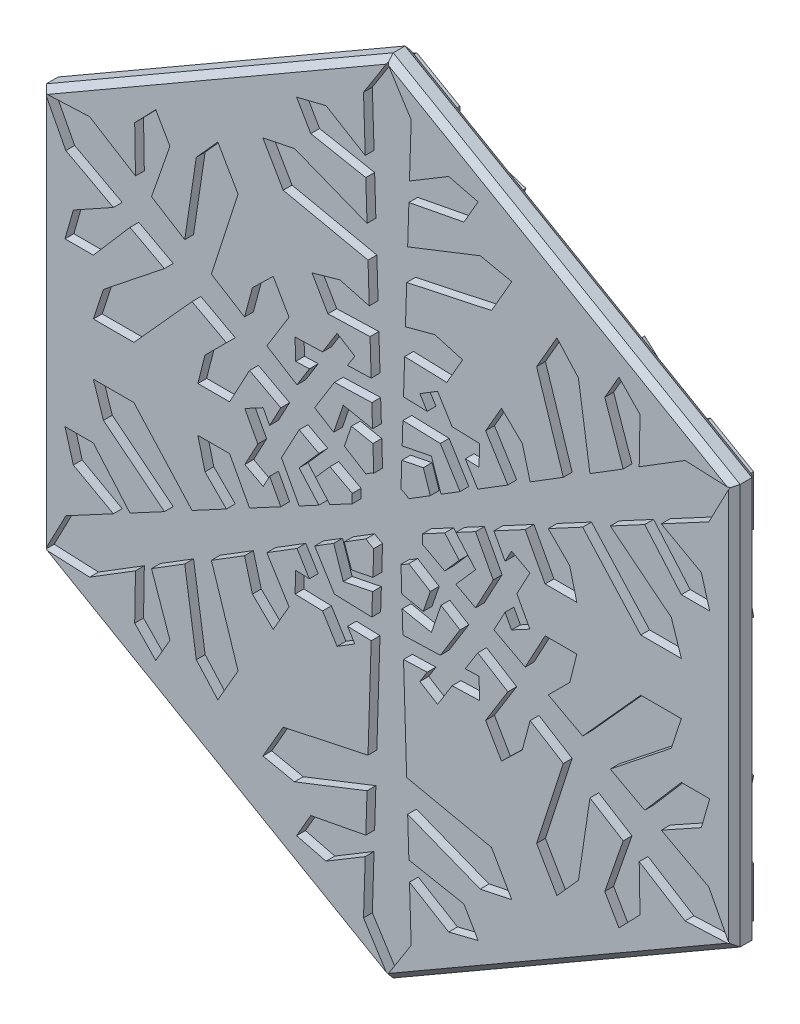
SolidWorks part; units mm, degrees
ref_plane "정면" through (0, 0, 0) normal (0, 0, 1) x (1, 0, 0)
ref_plane "윗면" through (0, 0, 0) normal (0, 1, 0) x (1, 0, 0)
ref_plane "우측면" through (0, 0, 0) normal (1, 0, 0) x (0, 0, -1)
sketch "스케치1" plane through (0, 0, 0) normal (0, 0, 1) x (1, 0, 0)
  line L0 (0, 0) -> (-56.2917, 32.5)
  line L1 (58.8897, -34) -> (58.8897, 34)
  line L2 (58.8897, 34) -> (0, 68)
  line L3 (0, 68) -> (-58.8897, 34)
  line L4 (-58.8897, 34) -> (-58.8897, -34)
  line L5 (-58.8897, -34) -> (0, -68)
  line L6 (0, -68) -> (58.8897, -34)
  line L7 (56.2917, 32.5) -> (0, 0)
  line L8 (0, -65) -> (0, 0)
  line L9 (-56.2917, 32.5) -> (-56.2917, -32.5)
  line L10 (-56.2917, -32.5) -> (0, -65)
  line L11 (0, -65) -> (56.2917, -32.5)
  line L12 (56.2917, -32.5) -> (56.2917, 32.5)
  line L13 (56.2917, 32.5) -> (0, 65)
  line L14 (0, 65) -> (-56.2917, 32.5)
  circle A1 centre (0, 0) radius 58.8897 construction
  point P1 (-58, 34.641)
  point P11 (0, -5)
  point P15 (0, -10)
  point P17 (-59, 32.909)
  point P20 (0, -15)
  point P21 (0, -20)
  point P22 (0, -25)
  point P23 (0, -30)
  point P24 (0, -35)
  point P25 (0, -40)
  point P26 (0, -45)
  point P27 (0, -50)
  point P28 (0, -55)
  point P29 (0, -60)
  point P32 (-4.3301, 2.3594)
  point P33 (-8.6603, 4.8594)
  point P34 (-12.9904, 7.3594)
  point P35 (-17.3205, 9.8594)
  point P36 (-21.6506, 12.3594)
  point P37 (-25.9808, 14.8594)
  point P38 (-30.3109, 17.3594)
  point P39 (-34.641, 19.8594)
  point P40 (-38.9711, 22.3594)
  point P41 (-43.3013, 24.8594)
  point P42 (-47.6314, 27.3594)
  point P43 (-51.9615, 29.8594)
  point P44 (4.2083, 2.4297)
  point P45 (8.5385, 4.9297)
  point P46 (12.8686, 7.4297)
  point P47 (17.1987, 9.9297)
  point P48 (21.5289, 12.4297)
  point P49 (25.859, 14.9297)
  point P50 (30.1891, 17.4297)
  point P51 (34.5192, 19.9297)
  point P52 (38.8494, 22.4297)
  point P53 (43.1795, 24.9297)
  point P54 (47.5096, 27.4297)
  point P55 (51.8397, 29.9297)
  point P56 (-0.0406, -0.0703)
  dimension "D1" = 65
  dimension "D2" = 5
  dimension "D3" = 12
  dimension "D4" = 3
  dimension "D5" = 65
  dimension "D6" = 65
  dimension "D7" = 65
  dimension "D8" = 68
extrude "보스-돌출1" add sketch "스케치1" along normal blind 5 contours L4 L5 L6 L1 L2 L3
sketch "스케치6" plane through (0, 0, 5) normal (0, 0, 1) x (1, 0, 0)
  line L1 (-58.8897, 34) -> (-58.0516, 33.5161)
  line L2 (-58.8897, 34) -> (-58.8897, -34)
  line L3 (0, 0) -> (-58.8897, 0) construction
  line L4 (-58.8897, -34) -> (0, -68)
  line L5 (0, -68) -> (0, 0)
  line L6 (0, 0) -> (-29.4449, -51) construction
  line L7 (-33.1527, -15.3513) -> (-27.313, -12.2197)
  line L8 (-54.5739, -26.8389) -> (-46.5066, -22.5127)
  line L9 (-46.5066, -22.5127) -> (-53.2967, -18.748)
  line L10 (-53.2967, -18.748) -> (-54.7146, -13.8014)
  line L11 (-54.7146, -13.8014) -> (-49.9016, -13.8014)
  line L12 (-49.9016, -13.8014) -> (-43.6834, -20.9987)
  line L13 (-37.8382, -17.864) -> (-48.1939, -9.622)
  line L14 (-48.1939, -9.622) -> (-49.9016, -4.4211)
  line L15 (-49.9016, -4.4211) -> (-43.0161, -4.4211)
  line L16 (-43.0161, -4.4211) -> (-33.1527, -15.3513)
  line L17 (-27.313, -12.2197) -> (-30.9566, -8.576)
  line L18 (-30.9566, -8.576) -> (-32.1611, -3.8066)
  line L19 (-32.1611, -3.8066) -> (-26.7746, -3.8066)
  line L20 (-26.7746, -3.8066) -> (-23.3909, -10.1164)
  line L21 (-18.0861, -7.2716) -> (-19.9799, -3.7402)
  line L22 (-24.196, 4.1218) -> (-21.0805, 5.7925)
  line L23 (-21.0805, 5.7925) -> (-19.9799, 3.7402)
  line L24 (-11.6248, -3.8066) -> (-14.9706, 0)
  line L25 (8.9871, -15.5661) -> (12.3358, -10.1645)
  line L26 (-12.1952, 0) -> (-9.7385, -2.795)
  line L27 (-50.5302, -33.8429) -> (-42.7498, -29.0196)
  line L28 (-6.0976, -10.5614) -> (-7.2898, -7.0363)
  line L29 (-43.6834, 20.9987) -> (-37.8382, 17.864)
  line L30 (-9.109, -8.1641) -> (-7.4853, -12.9649)
  line L31 (-5.5238, -21.1525) -> (-6.7509, -19.1732)
  line L32 (-8.5285, -23.0152) -> (-5.5238, -21.1525)
  line L33 (-15.3404, -12.0272) -> (-13.229, -15.433)
  line L34 (-16.6839, -21.2842) -> (-20.4564, -15.1989)
  line L35 (-19.3771, -25.9491) -> (-16.6839, -21.2842)
  line L36 (-22.9054, -22.5212) -> (-19.3771, -25.9491)
  line L37 (-24.239, -17.5439) -> (-22.9054, -22.5212)
  line L38 (-25.3368, -35.0424) -> (-29.871, -21.0354)
  line L39 (-28.7796, -41.0055) -> (-25.3368, -35.0424)
  line L40 (-32.4298, -36.9262) -> (-28.7796, -41.0055)
  line L41 (-34.3898, -23.8368) -> (-32.4298, -36.9262)
  line L42 (-36.9032, -36.3154) -> (-40.0271, -27.3316)
  line L43 (-39.3097, -40.4835) -> (-36.9032, -36.3154)
  line L44 (-42.8846, -36.7823) -> (-39.3097, -40.4835)
  line L45 (-42.7498, -29.0196) -> (-42.8846, -36.7823)
  line L48 (-50.5302, 33.8429) -> (-42.7498, 29.0196)
  line L49 (-42.7498, 29.0196) -> (-42.8846, 36.7823)
  line L50 (-42.8846, 36.7823) -> (-39.3097, 40.4835)
  line L51 (-39.3097, 40.4835) -> (-36.9032, 36.3154)
  line L52 (-36.9032, 36.3154) -> (-40.0271, 27.3316)
  line L53 (-34.3898, 23.8368) -> (-32.4298, 36.9262)
  line L54 (-32.4298, 36.9262) -> (-28.7796, 41.0055)
  line L55 (-28.7796, 41.0055) -> (-25.3368, 35.0424)
  line L56 (-25.3368, 35.0424) -> (-29.871, 21.0354)
  line L57 (-24.239, 17.5439) -> (-22.9054, 22.5212)
  line L58 (-22.9054, 22.5212) -> (-19.3771, 25.9491)
  line L59 (-19.3771, 25.9491) -> (-16.6839, 21.2842)
  line L60 (-16.6839, 21.2842) -> (-20.4564, 15.1989)
  line L61 (-15.3404, 12.0272) -> (-13.229, 15.433)
  line L62 (-9.109, 8.1641) -> (-7.4853, 12.9649)
  line L63 (-40.0271, 27.3316) -> (-34.3898, 23.8368)
  line L64 (-6.0976, 10.5614) -> (-7.2898, 7.0363)
  line L65 (-54.5739, 26.8389) -> (-46.5066, 22.5127)
  line L66 (-12.1952, 0) -> (-9.7385, 2.795)
  line L67 (-14.9706, 0) -> (-12.1952, 0)
  line L68 (-11.6248, 3.8066) -> (-14.9706, 0)
  line L69 (-21.0805, -5.7925) -> (-19.9799, -3.7402)
  line L70 (-24.196, -4.1218) -> (-21.0805, -5.7925)
  line L71 (-18.0861, 7.2716) -> (-19.9799, 3.7402)
  line L72 (-26.7746, 3.8066) -> (-23.3909, 10.1164)
  line L73 (-32.1611, 3.8066) -> (-26.7746, 3.8066)
  line L74 (-30.9566, 8.576) -> (-32.1611, 3.8066)
  line L75 (-27.313, 12.2197) -> (-30.9566, 8.576)
  line L76 (-43.0161, 4.4211) -> (-33.1527, 15.3513)
  line L77 (-49.9016, 4.4211) -> (-43.0161, 4.4211)
  line L78 (-48.1939, 9.622) -> (-49.9016, 4.4211)
  line L79 (-37.8382, 17.864) -> (-48.1939, 9.622)
  line L80 (-49.9016, 13.8014) -> (-43.6834, 20.9987)
  line L81 (-54.7146, 13.8014) -> (-49.9016, 13.8014)
  line L82 (-53.2967, 18.748) -> (-54.7146, 13.8014)
  line L83 (-46.5066, 22.5127) -> (-53.2967, 18.748)
  line L85 (-5.5238, 21.1525) -> (-6.7509, 19.1732)
  line L86 (-8.5285, 23.0152) -> (-5.5238, 21.1525)
  line L88 (4.0438, 60.6819) -> (3.7568, 51.5322)
  line L89 (3.7568, 51.5322) -> (10.4121, 55.5303)
  line L90 (10.4121, 55.5303) -> (15.4049, 54.285)
  line L91 (15.4049, 54.285) -> (12.9984, 50.1168)
  line L92 (12.9984, 50.1168) -> (3.6563, 48.3303)
  line L93 (3.4484, 41.7008) -> (15.7641, 46.5482)
  line L94 (15.7641, 46.5482) -> (21.122, 45.4266)
  line L95 (21.122, 45.4266) -> (17.6792, 39.4635)
  line L96 (17.6792, 39.4635) -> (3.2817, 36.3867)
  line L97 (3.0739, 29.7636) -> (8.0512, 31.0972)
  line L98 (8.0512, 31.0972) -> (12.784, 29.7556)
  line L99 (12.784, 29.7556) -> (10.0907, 25.0908)
  line L100 (10.0907, 25.0908) -> (2.9344, 25.3153)
  line L101 (2.7457, 19.2988) -> (6.7509, 19.1732)
  line L102 (2.5158, 11.9706) -> (7.4853, 12.9649)
  line L103 (-29.871, 21.0354) -> (-24.239, 17.5439)
  line L104 (6.0976, 10.5614) -> (2.4487, 9.8313)
  line L105 (-4.0438, 60.6819) -> (-3.7568, 51.5322)
  line L106 (-6.0976, 10.5614) -> (-2.4487, 9.8313)
  line L107 (-33.1527, 15.3513) -> (-27.313, 12.2197)
  line L108 (-2.5158, 11.9706) -> (-7.4853, 12.9649)
  line L109 (-15.5567, 15.36) -> (-13.229, 15.433)
  line L110 (-15.6676, 18.8935) -> (-15.5567, 15.36)
  line L111 (-2.7457, 19.2988) -> (-6.7509, 19.1732)
  line L112 (-10.0907, 25.0908) -> (-2.9344, 25.3153)
  line L113 (-12.784, 29.7556) -> (-10.0907, 25.0908)
  line L114 (-8.0512, 31.0972) -> (-12.784, 29.7556)
  line L115 (-3.0739, 29.7636) -> (-8.0512, 31.0972)
  line L116 (-17.6792, 39.4635) -> (-3.2817, 36.3867)
  line L117 (-21.122, 45.4266) -> (-17.6792, 39.4635)
  line L118 (-15.7641, 46.5482) -> (-21.122, 45.4266)
  line L119 (-3.4484, 41.7008) -> (-15.7641, 46.5482)
  line L120 (-12.9984, 50.1168) -> (-3.6563, 48.3303)
  line L121 (-15.4049, 54.285) -> (-12.9984, 50.1168)
  line L122 (-10.4121, 55.5303) -> (-15.4049, 54.285)
  line L123 (-3.7568, 51.5322) -> (-10.4121, 55.5303)
  line L125 (15.5567, 15.36) -> (13.229, 15.433)
  line L126 (15.6676, 18.8935) -> (15.5567, 15.36)
  line L128 (54.5739, 26.8389) -> (46.5066, 22.5127)
  line L129 (46.5066, 22.5127) -> (53.2967, 18.748)
  line L130 (53.2967, 18.748) -> (54.7146, 13.8014)
  line L131 (54.7146, 13.8014) -> (49.9016, 13.8014)
  line L132 (49.9016, 13.8014) -> (43.6834, 20.9987)
  line L133 (37.8382, 17.864) -> (48.1939, 9.622)
  line L134 (48.1939, 9.622) -> (49.9016, 4.4211)
  line L135 (49.9016, 4.4211) -> (43.0161, 4.4211)
  line L136 (43.0161, 4.4211) -> (33.1527, 15.3513)
  line L137 (27.313, 12.2197) -> (30.9566, 8.576)
  line L138 (30.9566, 8.576) -> (32.1611, 3.8066)
  line L139 (32.1611, 3.8066) -> (26.7746, 3.8066)
  line L140 (26.7746, 3.8066) -> (23.3909, 10.1164)
  line L141 (18.0861, 7.2716) -> (19.9799, 3.7402)
  line L142 (11.6248, 3.8066) -> (14.9706, 0)
  line L143 (-20.4564, 15.1989) -> (-15.3404, 12.0272)
  line L144 (12.1952, 0) -> (9.7385, 2.795)
  line L145 (50.5302, 33.8429) -> (42.7498, 29.0196)
  line L146 (6.0976, 10.5614) -> (7.2898, 7.0363)
  line L147 (7.2898, 7.0363) -> (3.6372, 4.7719)
  line L148 (9.109, 8.1641) -> (7.4853, 12.9649)
  line L149 (5.5238, 21.1525) -> (6.7509, 19.1732)
  line L150 (8.5285, 23.0152) -> (5.5238, 21.1525)
  line L151 (15.3404, 12.0272) -> (13.229, 15.433)
  line L152 (16.6839, 21.2842) -> (20.4564, 15.1989)
  line L153 (19.3771, 25.9491) -> (16.6839, 21.2842)
  line L154 (22.9054, 22.5212) -> (19.3771, 25.9491)
  line L155 (24.239, 17.5439) -> (22.9054, 22.5212)
  line L156 (25.3368, 35.0424) -> (29.871, 21.0354)
  line L157 (28.7796, 41.0055) -> (25.3368, 35.0424)
  line L158 (32.4298, 36.9262) -> (28.7796, 41.0055)
  line L159 (34.3898, 23.8368) -> (32.4298, 36.9262)
  line L160 (36.9032, 36.3154) -> (40.0271, 27.3316)
  line L161 (39.3097, 40.4835) -> (36.9032, 36.3154)
  line L162 (42.8846, 36.7823) -> (39.3097, 40.4835)
  line L163 (42.7498, 29.0196) -> (42.8846, 36.7823)
  line L165 (21.0805, -5.7925) -> (19.9799, -3.7402)
  line L166 (24.196, -4.1218) -> (21.0805, -5.7925)
  line L168 (50.5302, -33.8429) -> (42.7498, -29.0196)
  line L169 (42.7498, -29.0196) -> (42.8846, -36.7823)
  line L170 (42.8846, -36.7823) -> (39.3097, -40.4835)
  line L171 (39.3097, -40.4835) -> (36.9032, -36.3154)
  line L172 (36.9032, -36.3154) -> (40.0271, -27.3316)
  line L173 (34.3898, -23.8368) -> (32.4298, -36.9262)
  line L174 (32.4298, -36.9262) -> (28.7796, -41.0055)
  line L175 (28.7796, -41.0055) -> (25.3368, -35.0424)
  line L176 (25.3368, -35.0424) -> (29.871, -21.0354)
  line L177 (24.239, -17.5439) -> (22.9054, -22.5212)
  line L178 (22.9054, -22.5212) -> (19.3771, -25.9491)
  line L179 (19.3771, -25.9491) -> (16.6839, -21.2842)
  line L180 (16.6839, -21.2842) -> (20.4564, -15.1989)
  line L181 (15.3404, -12.0272) -> (13.229, -15.433)
  line L182 (9.109, -8.1641) -> (7.4853, -12.9649)
  line L183 (-23.3909, 10.1164) -> (-18.0861, 7.2716)
  line L184 (6.0976, -10.5614) -> (7.2898, -7.0363)
  line L185 (54.5739, -26.8389) -> (46.5066, -22.5127)
  line L186 (12.1952, 0) -> (9.7385, -2.795)
  line L187 (-3.6563, 48.3303) -> (-3.4484, 41.7008)
  line L188 (11.6248, -3.8066) -> (14.9706, 0)
  line L189 (21.0805, 5.7925) -> (19.9799, 3.7402)
  line L190 (24.196, 4.1218) -> (21.0805, 5.7925)
  line L191 (18.0861, -7.2716) -> (19.9799, -3.7402)
  line L192 (26.7746, -3.8066) -> (23.3909, -10.1164)
  line L193 (32.1611, -3.8066) -> (26.7746, -3.8066)
  line L194 (30.9566, -8.576) -> (32.1611, -3.8066)
  line L195 (27.313, -12.2197) -> (30.9566, -8.576)
  line L196 (43.0161, -4.4211) -> (33.1527, -15.3513)
  line L197 (49.9016, -4.4211) -> (43.0161, -4.4211)
  line L198 (48.1939, -9.622) -> (49.9016, -4.4211)
  line L199 (37.8382, -17.864) -> (48.1939, -9.622)
  line L200 (49.9016, -13.8014) -> (43.6834, -20.9987)
  line L201 (54.7146, -13.8014) -> (49.9016, -13.8014)
  line L202 (53.2967, -18.748) -> (54.7146, -13.8014)
  line L203 (46.5066, -22.5127) -> (53.2967, -18.748)
  line L205 (5.5238, -21.1525) -> (6.7509, -19.1732)
  line L206 (8.5285, -23.0152) -> (5.5238, -21.1525)
  line L208 (-4.0438, -60.6819) -> (-3.7568, -51.5322)
  line L209 (-3.7568, -51.5322) -> (-10.4121, -55.5303)
  line L210 (-10.4121, -55.5303) -> (-15.4049, -54.285)
  line L211 (-15.4049, -54.285) -> (-12.9984, -50.1168)
  line L212 (-12.9984, -50.1168) -> (-3.6563, -48.3303)
  line L213 (-3.4484, -41.7008) -> (-15.7641, -46.5482)
  line L214 (-15.7641, -46.5482) -> (-21.122, -45.4266)
  line L215 (-21.122, -45.4266) -> (-17.6792, -39.4635)
  line L216 (-17.6792, -39.4635) -> (-3.2817, -36.3867)
  line L217 (-3.0739, -29.7636) -> (-8.0512, -31.0972)
  line L218 (-8.0512, -31.0972) -> (-12.784, -29.7556)
  line L219 (-12.784, -29.7556) -> (-10.0907, -25.0908)
  line L220 (-10.0907, -25.0908) -> (-2.9344, -25.3153)
  line L221 (-2.7457, -19.2988) -> (-6.7509, -19.1732)
  line L222 (-2.5158, -11.9706) -> (-7.4853, -12.9649)
  line L223 (-7.4853, -12.9649) -> (-6.0976, -10.5614)
  line L224 (-6.0976, -10.5614) -> (-2.4487, -9.8313)
  line L225 (4.0438, -60.6819) -> (3.7568, -51.5322)
  line L226 (6.0976, -10.5614) -> (2.4487, -9.8313)
  line L227 (3.6563, 48.3303) -> (3.4484, 41.7008)
  line L228 (2.5158, -11.9706) -> (7.4853, -12.9649)
  line L229 (15.5567, -15.36) -> (13.229, -15.433)
  line L230 (15.6676, -18.8935) -> (15.5567, -15.36)
  line L231 (2.7457, -19.2988) -> (6.7509, -19.1732)
  line L232 (10.0907, -25.0908) -> (2.9344, -25.3153)
  line L233 (12.784, -29.7556) -> (10.0907, -25.0908)
  line L234 (8.0512, -31.0972) -> (12.784, -29.7556)
  line L235 (3.0739, -29.7636) -> (8.0512, -31.0972)
  line L236 (17.6792, -39.4635) -> (3.2817, -36.3867)
  line L237 (21.122, -45.4266) -> (17.6792, -39.4635)
  line L238 (15.7641, -46.5482) -> (21.122, -45.4266)
  line L239 (3.4484, -41.7008) -> (15.7641, -46.5482)
  line L240 (12.9984, -50.1168) -> (3.6563, -48.3303)
  line L241 (15.4049, -54.285) -> (12.9984, -50.1168)
  line L242 (10.4121, -55.5303) -> (15.4049, -54.285)
  line L243 (3.7568, -51.5322) -> (10.4121, -55.5303)
  line L245 (-15.5567, -15.36) -> (-13.229, -15.433)
  line L246 (-15.6676, -18.8935) -> (-15.5567, -15.36)
  line L247 (-10.9928, 19.0401) -> (-15.6676, 18.8935)
  line L248 (-10.9928, 19.0401) -> (-8.5285, 23.0152)
  line L249 (-8.9871, 15.5661) -> (-12.3358, 10.1645)
  line L250 (-8.9871, 15.5661) -> (-2.6348, 15.7653)
  line L251 (10.9928, 19.0401) -> (15.6676, 18.8935)
  line L252 (8.9871, 15.5661) -> (12.3358, 10.1645)
  line L253 (10.9928, 19.0401) -> (8.5285, 23.0152)
  line L254 (8.9871, 15.5661) -> (2.6348, 15.7653)
  line L255 (17.9742, 0) -> (14.9706, -5.6008)
  line L256 (21.9856, 0) -> (24.196, -4.1218)
  line L257 (17.9742, 0) -> (14.9706, 5.6008)
  line L258 (21.9856, 0) -> (24.196, 4.1218)
  line L259 (8.9871, -15.5661) -> (2.6348, -15.7653)
  line L260 (10.9928, -19.0401) -> (15.6676, -18.8935)
  line L261 (10.9928, -19.0401) -> (8.5285, -23.0152)
  line L262 (-10.9928, -19.0401) -> (-8.5285, -23.0152)
  line L263 (-8.9871, -15.5661) -> (-2.6348, -15.7653)
  line L264 (-8.9871, -15.5661) -> (-12.3358, -10.1645)
  line L265 (-10.9928, -19.0401) -> (-15.6676, -18.8935)
  line L266 (-21.9856, 0) -> (-24.196, 4.1218)
  line L267 (-21.9856, 0) -> (-24.196, -4.1218)
  line L268 (-17.9742, 0) -> (-14.9706, -5.6008)
  line L269 (-17.9742, 0) -> (-14.9706, 5.6008)
  line L270 (-50.5302, 33.8429) -> (-58.0516, 33.5161)
  line L271 (-58.0516, 33.5161) -> (-54.5739, 26.8389)
  line L272 (4.0438, 60.6819) -> (0, 67.0322)
  line L273 (0, 67.0322) -> (-4.0438, 60.6819)
  line L274 (-3.2817, 36.3867) -> (-3.0739, 29.7636)
  line L275 (3.2817, 36.3867) -> (3.0739, 29.7636)
  line L276 (-2.9344, 25.3153) -> (-2.7457, 19.2988)
  line L277 (2.9344, 25.3153) -> (2.7457, 19.2988)
  line L278 (-2.6348, 15.7653) -> (-2.5158, 11.9706)
  line L279 (2.6348, 15.7653) -> (2.5158, 11.9706)
  line L280 (-2.4487, 9.8313) -> (-2.314, 5.5358)
  line L281 (2.4487, 9.8313) -> (2.314, 5.5358)
  line L282 (9.7385, 2.795) -> (5.9512, 0.764)
  line L283 (9.7385, -2.795) -> (5.9512, -0.764)
  line L284 (7.2898, -7.0363) -> (3.6372, -4.7719)
  line L285 (-2.4487, -9.8313) -> (-2.314, -5.5358)
  line L286 (2.4487, -9.8313) -> (2.314, -5.5358)
  line L287 (-7.2898, -7.0363) -> (-3.6372, -4.7719)
  line L288 (-9.7385, -2.795) -> (-5.9512, -0.764)
  line L289 (-9.7385, 2.795) -> (-5.9512, 0.764)
  line L290 (-7.2898, 7.0363) -> (-3.6372, 4.7719)
  line L291 (12.3358, -10.1645) -> (9.109, -8.1641)
  line L292 (14.9706, -5.6008) -> (11.6248, -3.8066)
  line L293 (2.6348, -15.7653) -> (2.5158, -11.9706)
  line L294 (-2.6348, -15.7653) -> (-2.5158, -11.9706)
  line L295 (-12.3358, -10.1645) -> (-9.109, -8.1641)
  line L296 (-14.9706, -5.6008) -> (-11.6248, -3.8066)
  line L297 (-14.9706, 5.6008) -> (-11.6248, 3.8066)
  line L298 (-12.3358, 10.1645) -> (-9.109, 8.1641)
  line L299 (20.4564, -15.1989) -> (15.3404, -12.0272)
  line L300 (23.3909, -10.1164) -> (18.0861, -7.2716)
  line L301 (33.1527, -15.3513) -> (27.313, -12.2197)
  line L302 (29.871, -21.0354) -> (24.239, -17.5439)
  line L303 (40.0271, -27.3316) -> (34.3898, -23.8368)
  line L304 (43.6834, -20.9987) -> (37.8382, -17.864)
  line L305 (3.2817, -36.3867) -> (2.7457, -19.2988)
  line L306 (-3.2817, -36.3867) -> (-2.7457, -19.2988)
  line L307 (-3.6563, -48.3303) -> (-3.4484, -41.7008)
  line L308 (3.6563, -48.3303) -> (3.4484, -41.7008)
  line L309 (-29.871, -21.0354) -> (-24.239, -17.5439)
  line L310 (-40.0271, -27.3316) -> (-34.3898, -23.8368)
  line L311 (-43.6834, -20.9987) -> (-37.8382, -17.864)
  line L312 (-23.3909, -10.1164) -> (-18.0861, -7.2716)
  line L313 (-20.4564, -15.1989) -> (-15.3404, -12.0272)
  line L314 (14.9706, 5.6008) -> (11.6248, 3.8066)
  line L315 (12.3358, 10.1645) -> (9.109, 8.1641)
  line L316 (20.4564, 15.1989) -> (15.3404, 12.0272)
  line L317 (23.3909, 10.1164) -> (18.0861, 7.2716)
  line L318 (33.1527, 15.3513) -> (27.313, 12.2197)
  line L319 (29.871, 21.0354) -> (24.239, 17.5439)
  line L320 (40.0271, 27.3316) -> (34.3898, 23.8368)
  line L321 (43.6834, 20.9987) -> (37.8382, 17.864)
  line L322 (54.5739, 26.8389) -> (58.0516, 33.5161)
  line L323 (58.0516, 33.5161) -> (50.5302, 33.8429)
  line L324 (50.5302, -33.8429) -> (58.0516, -33.5161)
  line L325 (58.0516, -33.5161) -> (54.5739, -26.8389)
  line L326 (-4.0438, -60.6819) -> (0, -67.0322)
  line L327 (0, -67.0322) -> (4.0438, -60.6819)
  line L328 (-54.5739, -26.8389) -> (-58.0516, -33.5161)
  line L329 (-58.0516, -33.5161) -> (-50.5302, -33.8429)
  arc A0 (2.314, -5.5358) -> (3.6372, -4.7719) centre (0, 0) ccw
  arc A1 (-3.6372, -4.7719) -> (-2.314, -5.5358) centre (0, 0) ccw
  arc A2 (-5.9512, 0.764) -> (-5.9512, -0.764) centre (0, 0) ccw
  arc A3 (-2.314, 5.5358) -> (-3.6372, 4.7719) centre (0, 0) ccw
  arc A4 (3.6372, 4.7719) -> (2.314, 5.5358) centre (0, 0) ccw
  arc A5 (5.9512, -0.764) -> (5.9512, 0.764) centre (0, 0) ccw
  point P319 (0, 0)
  point P353 (0, 0)
  dimension "D1" = 12
extrude "컷-돌출8" cut sketch "스케치6" against normal blind 1.5
sketch "스케치7" plane through (0, 0, 0) normal (0, 0, -1) x (-1, 0, 0)
  line L0 (-57.1635, -33.0033) -> (-57.1635, -24.5668)
  line L1 (0, 0) -> (-58.8897, -34)
  line L2 (0, -68) -> (-58.8897, -34) construction
  line L3 (-58.8897, -34) -> (-58.8897, 34) construction
  line L4 (-57.1635, -24.5668) -> (-53.949, -22.7109)
  line L5 (-53.949, -22.7109) -> (-49.5128, -25.6103)
  line L6 (-33.7718, -16.3007) -> (-39.9086, -19.9302)
  line L7 (-42.3815, -21.3927) -> (-51.3689, -16.3226)
  line L8 (-51.3689, -16.3226) -> (-55.9662, -17.3111)
  line L9 (-55.9662, -17.3111) -> (-57.186, -11.6378)
  line L10 (-57.186, -11.6378) -> (-49.5697, -10.0002)
  line L11 (-49.5697, -10.0002) -> (-49.5697, -14.4801)
  line L12 (-49.5697, -14.4801) -> (-39.9086, -19.9302)
  line L13 (-42.3815, -21.3927) -> (-49.5128, -25.6103)
  line L14 (-39.7173, -26.0071) -> (-46.9355, -30.0742)
  line L15 (-37.325, -35.6885) -> (-37.2143, -24.5968)
  line L16 (-33.4453, -37.9285) -> (-37.325, -35.6885)
  line L17 (-38.6716, -43.7056) -> (-33.4453, -37.9285)
  line L18 (-42.9749, -39.8126) -> (-38.6716, -43.7056)
  line L19 (-39.8203, -36.3254) -> (-42.9749, -39.8126)
  line L20 (-39.7173, -26.0071) -> (-39.8203, -36.3254)
  line L21 (-31.0027, -21.0969) -> (-37.2143, -24.5968)
  line L22 (-46.6427, -35.3658) -> (-46.9355, -30.0742)
  line L23 (-49.8572, -37.2216) -> (-46.6427, -35.3658)
  line L24 (-57.1635, -33.0033) -> (-49.8572, -37.2216)
  line L25 (-57.1635, 33.0033) -> (-49.8572, 37.2216)
  line L26 (-49.8572, 37.2216) -> (-46.6427, 35.3658)
  line L27 (-46.6427, 35.3658) -> (-46.9355, 30.0742)
  line L28 (-31.0027, 21.0969) -> (-37.2143, 24.5968)
  line L29 (-39.7173, 26.0071) -> (-39.8203, 36.3254)
  line L30 (-39.8203, 36.3254) -> (-42.9749, 39.8126)
  line L31 (-42.9749, 39.8126) -> (-38.6716, 43.7056)
  line L32 (-38.6716, 43.7056) -> (-33.4453, 37.9285)
  line L33 (-33.4453, 37.9285) -> (-37.325, 35.6885)
  line L34 (-37.325, 35.6885) -> (-37.2143, 24.5968)
  line L35 (-39.7173, 26.0071) -> (-46.9355, 30.0742)
  line L36 (-42.3815, 21.3927) -> (-49.5128, 25.6103)
  line L37 (-49.5697, 14.4801) -> (-39.9086, 19.9302)
  line L38 (-49.5697, 10.0002) -> (-49.5697, 14.4801)
  line L39 (-57.186, 11.6378) -> (-49.5697, 10.0002)
  line L40 (-55.9662, 17.3111) -> (-57.186, 11.6378)
  line L41 (-51.3689, 16.3226) -> (-55.9662, 17.3111)
  line L42 (-42.3815, 21.3927) -> (-51.3689, 16.3226)
  line L43 (-33.7718, 16.3007) -> (-39.9086, 19.9302)
  line L44 (-53.949, 22.7109) -> (-49.5128, 25.6103)
  line L45 (-57.1635, 24.5668) -> (-53.949, 22.7109)
  line L46 (-57.1635, 33.0033) -> (-57.1635, 24.5668)
  line L47 (0, 66.0067) -> (7.3063, 61.7884)
  line L48 (7.3063, 61.7884) -> (7.3063, 58.0767)
  line L49 (7.3063, 58.0767) -> (2.5772, 55.6844)
  line L50 (2.7691, 37.3976) -> (2.6943, 44.527)
  line L51 (2.6642, 47.3998) -> (11.5486, 52.6481)
  line L52 (11.5486, 52.6481) -> (12.9912, 57.1237)
  line L53 (12.9912, 57.1237) -> (18.5143, 55.3434)
  line L54 (18.5143, 55.3434) -> (16.1244, 47.9287)
  line L55 (16.1244, 47.9287) -> (12.2447, 50.1686)
  line L56 (12.2447, 50.1686) -> (2.6943, 44.527)
  line L57 (2.6642, 47.3998) -> (2.5772, 55.6844)
  line L58 (-2.6642, 47.3998) -> (-2.5772, 55.6844)
  line L59 (-12.2447, 50.1686) -> (-2.6943, 44.527)
  line L60 (-16.1244, 47.9287) -> (-12.2447, 50.1686)
  line L61 (-18.5143, 55.3434) -> (-16.1244, 47.9287)
  line L62 (-12.9912, 57.1237) -> (-18.5143, 55.3434)
  line L63 (-11.5486, 52.6481) -> (-12.9912, 57.1237)
  line L64 (-2.6642, 47.3998) -> (-11.5486, 52.6481)
  line L65 (-2.7691, 37.3976) -> (-2.6943, 44.527)
  line L66 (-7.3063, 58.0767) -> (-2.5772, 55.6844)
  line L67 (-7.3063, 61.7884) -> (-7.3063, 58.0767)
  line L68 (0, 66.0067) -> (-7.3063, 61.7884)
  line L69 (57.1635, 33.0033) -> (57.1635, 24.5668)
  line L70 (57.1635, 24.5668) -> (53.949, 22.7109)
  line L71 (53.949, 22.7109) -> (49.5128, 25.6103)
  line L72 (33.7718, 16.3007) -> (39.9086, 19.9302)
  line L73 (42.3815, 21.3927) -> (51.3689, 16.3226)
  line L74 (51.3689, 16.3226) -> (55.9662, 17.3111)
  line L75 (55.9662, 17.3111) -> (57.186, 11.6378)
  line L76 (57.186, 11.6378) -> (49.5697, 10.0002)
  line L77 (49.5697, 10.0002) -> (49.5697, 14.4801)
  line L78 (49.5697, 14.4801) -> (39.9086, 19.9302)
  line L79 (42.3815, 21.3927) -> (49.5128, 25.6103)
  line L80 (39.7173, 26.0071) -> (46.9355, 30.0742)
  line L81 (37.325, 35.6885) -> (37.2143, 24.5968)
  line L82 (33.4453, 37.9285) -> (37.325, 35.6885)
  line L83 (38.6716, 43.7056) -> (33.4453, 37.9285)
  line L84 (42.9749, 39.8126) -> (38.6716, 43.7056)
  line L85 (39.8203, 36.3254) -> (42.9749, 39.8126)
  line L86 (39.7173, 26.0071) -> (39.8203, 36.3254)
  line L87 (31.0027, 21.0969) -> (37.2143, 24.5968)
  line L88 (46.6427, 35.3658) -> (46.9355, 30.0742)
  line L89 (49.8572, 37.2216) -> (46.6427, 35.3658)
  line L90 (57.1635, 33.0033) -> (49.8572, 37.2216)
  line L91 (57.1635, -33.0033) -> (49.8572, -37.2216)
  line L92 (49.8572, -37.2216) -> (46.6427, -35.3658)
  line L93 (46.6427, -35.3658) -> (46.9355, -30.0742)
  line L94 (31.0027, -21.0969) -> (37.2143, -24.5968)
  line L95 (39.7173, -26.0071) -> (39.8203, -36.3254)
  line L96 (39.8203, -36.3254) -> (42.9749, -39.8126)
  line L97 (42.9749, -39.8126) -> (38.6716, -43.7056)
  line L98 (38.6716, -43.7056) -> (33.4453, -37.9285)
  line L99 (33.4453, -37.9285) -> (37.325, -35.6885)
  line L100 (37.325, -35.6885) -> (37.2143, -24.5968)
  line L101 (39.7173, -26.0071) -> (46.9355, -30.0742)
  line L102 (42.3815, -21.3927) -> (49.5128, -25.6103)
  line L103 (49.5697, -14.4801) -> (39.9086, -19.9302)
  line L104 (49.5697, -10.0002) -> (49.5697, -14.4801)
  line L105 (57.186, -11.6378) -> (49.5697, -10.0002)
  line L106 (55.9662, -17.3111) -> (57.186, -11.6378)
  line L107 (51.3689, -16.3226) -> (55.9662, -17.3111)
  line L108 (42.3815, -21.3927) -> (51.3689, -16.3226)
  line L109 (33.7718, -16.3007) -> (39.9086, -19.9302)
  line L110 (53.949, -22.7109) -> (49.5128, -25.6103)
  line L111 (57.1635, -24.5668) -> (53.949, -22.7109)
  line L112 (57.1635, -33.0033) -> (57.1635, -24.5668)
  line L113 (0, -66.0067) -> (-7.3063, -61.7884)
  line L114 (-7.3063, -61.7884) -> (-7.3063, -58.0767)
  line L115 (-7.3063, -58.0767) -> (-2.5772, -55.6844)
  line L116 (-2.7691, -37.3976) -> (-2.6943, -44.527)
  line L117 (-2.6642, -47.3998) -> (-11.5486, -52.6481)
  line L118 (-11.5486, -52.6481) -> (-12.9912, -57.1237)
  line L119 (-12.9912, -57.1237) -> (-18.5143, -55.3434)
  line L120 (-18.5143, -55.3434) -> (-16.1244, -47.9287)
  line L121 (-16.1244, -47.9287) -> (-12.2447, -50.1686)
  line L122 (-12.2447, -50.1686) -> (-2.6943, -44.527)
  line L123 (-2.6642, -47.3998) -> (-2.5772, -55.6844)
  line L124 (2.6642, -47.3998) -> (2.5772, -55.6844)
  line L125 (12.2447, -50.1686) -> (2.6943, -44.527)
  line L126 (16.1244, -47.9287) -> (12.2447, -50.1686)
  line L127 (18.5143, -55.3434) -> (16.1244, -47.9287)
  line L128 (12.9912, -57.1237) -> (18.5143, -55.3434)
  line L129 (11.5486, -52.6481) -> (12.9912, -57.1237)
  line L130 (2.6642, -47.3998) -> (11.5486, -52.6481)
  line L131 (2.7691, -37.3976) -> (2.6943, -44.527)
  line L132 (7.3063, -58.0767) -> (2.5772, -55.6844)
  line L133 (7.3063, -61.7884) -> (7.3063, -58.0767)
  line L134 (0, -66.0067) -> (7.3063, -61.7884)
  line L135 (-49.5128, -28.5862) -> (-53.949, -25.6103)
  line L136 (-53.949, -25.6103) -> (-55.9662, -26.7749)
  line L137 (-55.9662, -26.7749) -> (-55.9662, -32.3121)
  line L138 (-49.5128, -28.5862) -> (-49.1537, -33.9161)
  line L139 (-49.1537, -33.9161) -> (-51.1708, -35.0807)
  line L140 (-51.1708, -35.0807) -> (-55.9662, -32.3121)
  line L141 (-49.5128, 28.5862) -> (-49.1537, 33.9161)
  line L142 (-49.1537, 33.9161) -> (-51.1708, 35.0807)
  line L143 (-51.1708, 35.0807) -> (-55.9662, 32.3121)
  line L144 (-55.9662, 26.7749) -> (-55.9662, 32.3121)
  line L145 (-53.949, 25.6103) -> (-55.9662, 26.7749)
  line L146 (-49.5128, 28.5862) -> (-53.949, 25.6103)
  line L147 (0, 57.1724) -> (4.7954, 59.5264)
  line L148 (4.7954, 59.5264) -> (4.7954, 61.8556)
  line L149 (4.7954, 61.8556) -> (0, 64.6242)
  line L150 (-4.7954, 61.8556) -> (0, 64.6242)
  line L151 (-4.7954, 59.5264) -> (-4.7954, 61.8556)
  line L152 (0, 57.1724) -> (-4.7954, 59.5264)
  line L153 (49.5128, 28.5862) -> (53.949, 25.6103)
  line L154 (53.949, 25.6103) -> (55.9662, 26.7749)
  line L155 (55.9662, 26.7749) -> (55.9662, 32.3121)
  line L156 (51.1708, 35.0807) -> (55.9662, 32.3121)
  line L157 (49.1537, 33.9161) -> (51.1708, 35.0807)
  line L158 (49.5128, 28.5862) -> (49.1537, 33.9161)
  line L159 (49.5128, -28.5862) -> (49.1537, -33.9161)
  line L160 (49.1537, -33.9161) -> (51.1708, -35.0807)
  line L161 (51.1708, -35.0807) -> (55.9662, -32.3121)
  line L162 (55.9662, -26.7749) -> (55.9662, -32.3121)
  line L163 (53.949, -25.6103) -> (55.9662, -26.7749)
  line L164 (49.5128, -28.5862) -> (53.949, -25.6103)
  line L165 (0, -57.1724) -> (-4.7954, -59.5264)
  line L166 (-4.7954, -59.5264) -> (-4.7954, -61.8556)
  line L167 (-4.7954, -61.8556) -> (0, -64.6242)
  line L168 (4.7954, -61.8556) -> (0, -64.6242)
  line L169 (4.7954, -59.5264) -> (4.7954, -61.8556)
  line L170 (0, -57.1724) -> (4.7954, -59.5264)
  circle A0 centre (0, 0) radius 37.5
  point P151 (0, 0)
  point P187 (0, 0)
  dimension "D1" = 75
extrude "컷-돌출9" cut sketch "스케치7" against normal blind 1 contours A0 L87 L81 L82 L83 L84 L85 L86 L80 L88 L89 L90 L69 L70 L71 L79 L73 L74 L75 L76 L77 L78 L72 L109 L103 L104 L105 L106 L107 L108 L102 L110 L111 L112 L91 L92 L93 L101 L95 L96 L97 L98 L99 L100 L94 L131 L125 L126 L127 | L146 L141 L142 L143 L144 L145 | L140 L139 L138 L1 | L136 L137 L1 L135 | L152 L147 L148 L149 L150 L151 | L158 L153 L154 L155 L156 L157 | L164 L159 L160 L161 L162 L163 | L170 L165 L166 L167 L168 L169
sketch "스케치8" plane through (0, 0, 0) normal (0, 0, -1) x (-1, 0, 0)
  circle A0 centre (0, 0) radius 35
  dimension "D1" = 70
extrude "컷-돌출10" cut sketch "스케치8" against normal blind 2
chamfer "모따기1" distance 1 angle 45 12 edges at (29.4449, -51, 5) (-29.4449, -51, 5) (-58.8897, 0, 5) (-29.4449, 51, 5) (29.4449, 51, 5) (58.8897, 0, 5) (29.4449, -51, 1) (-29.4449, -51, 1) (-58.8897, 0, 1) (-29.4449, 51, 1) (58.8897, 0, 1) (29.4449, 51, 1)
